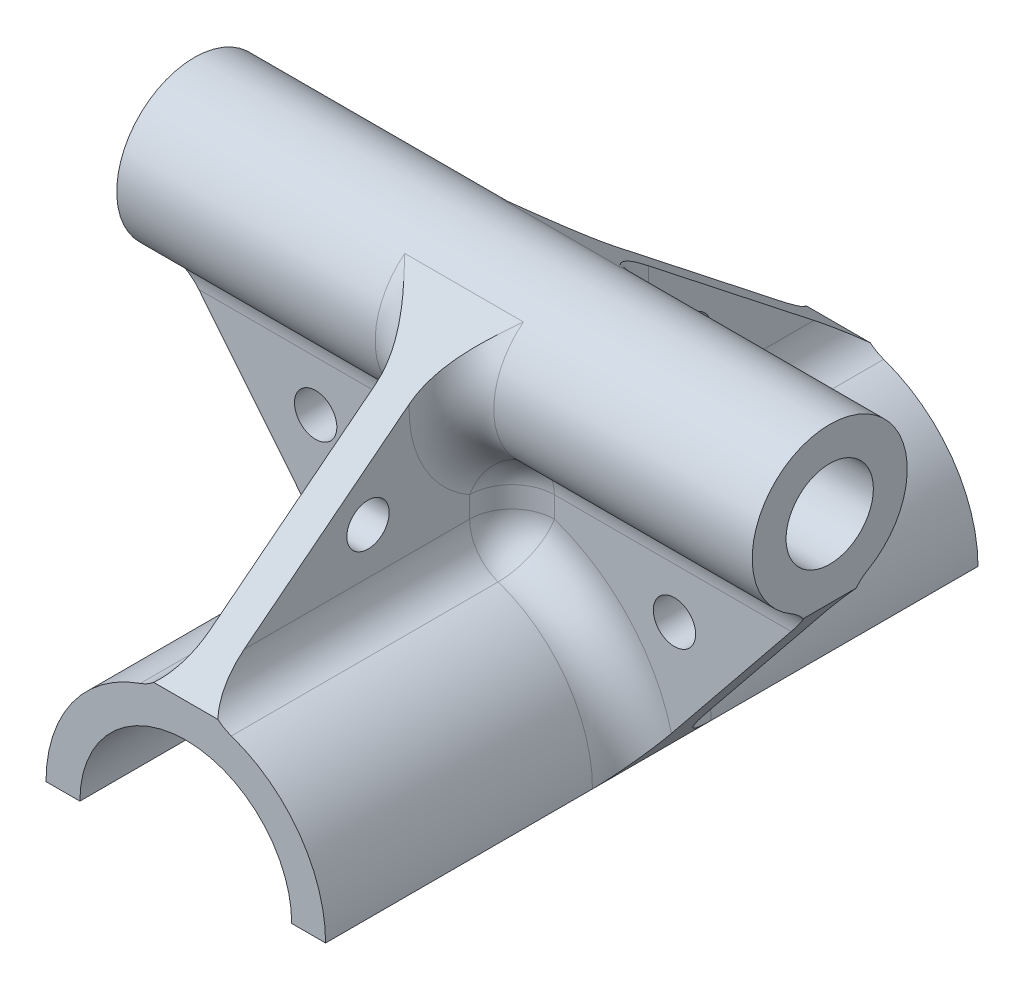
SolidWorks part; units mm, degrees
material "ABS"
ref_plane "Front Plane" through (0, 0, 0) normal (0, 0, 1) x (1, 0, 0)
ref_plane "Top Plane" through (0, 0, 0) normal (0, 1, 0) x (1, 0, 0)
ref_plane "Right Plane" through (0, 0, 0) normal (1, 0, 0) x (0, 0, -1)
sketch "Sketch2" plane through (0, 0, 0) normal (0, 0, 1) x (1, 0, 0)
  line L0 (-16.5, 0) -> (-12.5, 0)
  line L1 (12.5, 0) -> (16.5, 0)
  arc A0 (16.5, 0) -> (-16.5, 0) centre (0, 0) ccw
  arc A1 (12.5, 0) -> (-12.5, 0) centre (0, 0) ccw
  dimension "D1" = 4
  dimension "D2" = 25
extrude "Fuselage mount" add sketch "Sketch2" along normal blind 77
sketch "Sketch3" plane through (0, 0, 0) normal (1, 0, 0) x (0, 0, -1)
  line L0 (-38.5, 16.5) -> (-38.5, 35.1181) construction
  line L1 (0, 16.5) -> (-77, 16.5) construction
  circle A0 centre (-38.5, 35.1181) radius 9.15
  circle A1 centre (-38.5, 35.1181) radius 5.15
  dimension "D2" = 10.3
  dimension "D3" = 18.6181
  dimension "D1" = 4
extrude "Spar mount" add sketch "Sketch3" along normal blind 37.5 and the other way blind 37.5 separate body
ref_plane "Plane1" through (0, 0, 38.5) normal (0, 0, 1) x (1, 0, 0)
sketch "Sketch8" plane through (0, 0, 0) normal (1, 0, 0) x (0, 0, -1)
  line L0 (-77, 16.5) -> (-44.1537, 42.3124)
  line L1 (0, 16.5) -> (-32.8463, 42.3124)
  line L2 (-77, 16.5) -> (-77, 12.5)
  line L3 (-77, 16.5) -> (-77, 0) construction
  line L4 (-77, 12.5) -> (0, 12.5)
  line L5 (0, 0) -> (0, 16.5) construction
  line L6 (0, 12.5) -> (0, 16.5)
  circle A0 centre (-38.5, 35.1181) radius 9.15 construction
  arc A1 (-44.1537, 42.3124) -> (-32.8463, 42.3124) centre (-38.5, 35.1181) ccw
extrude "Boss-Extrude1" add sketch "Sketch8" along normal blind 2 and the other way blind 2
sketch "Sketch9" plane through (0, 0, 38.5) normal (0, 0, 1) x (1, 0, 0)
  line L0 (-16.5, 0) -> (-37.5, 25.9681)
  line L1 (-37.5, 25.9681) -> (-37.5, 29.9681)
  line L2 (-37.5, 44.2681) -> (-37.5, 25.9681) construction
  line L3 (-37.5, 29.9681) -> (-2, 29.9681)
  line L4 (-2, 42.3124) -> (-2, 25.9681) construction
  line L5 (-2, 29.9681) -> (-2, 16.3783)
  line L8 (0, 0) -> (0, 50000) construction
  line L9 (2, 29.9681) -> (2, 16.3783)
  line L10 (37.5, 29.9681) -> (2, 29.9681)
  line L11 (37.5, 25.9681) -> (37.5, 29.9681)
  line L12 (16.5, 0) -> (37.5, 25.9681)
  arc A0 (-16.5, 0) -> (-2, 16.3783) centre (0, 0) cw
  arc A1 (-2, 16.3783) -> (-16.5, 0) centre (0, 0) ccw construction
  arc A2 (16.5, 0) -> (2, 16.3783) centre (0, 0) ccw
extrude "Boss-Extrude2" add sketch "Sketch9" along normal blind 2 and the other way blind 2
fillet "Fillet1" radius 5 20 edges at (-2, 33.0959, 47.4237) (-2, 16.3783, 58.75) (-2, 21.2838, 40.5) (-12.3541, 10.9373, 40.5) (-19.75, 26.1894, 40.5) (-2, 33.0959, 29.5763) (-2, 21.2838, 36.5) (-19.75, 26.1894, 36.5) (-12.3541, 10.9373, 36.5) (-2, 16.3783, 18.25) (19.75, 26.1894, 40.5) (19.75, 26.1894, 36.5) (2, 33.0959, 29.5763) (12.3541, 10.9373, 36.5) (2, 21.2838, 36.5) (2, 16.3783, 18.25) (2, 33.0959, 47.4237) (2, 21.2838, 40.5) (2, 16.3783, 58.75) (12.3541, 10.9373, 40.5)
sketch "Sketch10" plane through (2, 0, 0) normal (1, 0, 0) x (0, 0, -1)
  line L0 (-4.8718, 20.3286) -> (-26.1375, 28.2339) construction
  line L1 (-38.5, 35.69) -> (-38.5, -49964.31) construction
  line L2 (-14.6158, 27.9859) -> (-31.5, 20.3286) construction
  line L4 (-31.5, 20.3286) -> (-4.8718, 20.3286) construction
  line L5 (-4.8718, 20.3286) -> (-24.3597, 35.6432) construction
  arc A3 (-31.5, 22.8208) -> (-24.3597, 35.6432) centre (-38.5, 35.1181) ccw construction
  point P0 (-19.5052, 25.7684)
  point P1 (-57.4948, 25.7684)
hole_wizard "Ø5.0 (5) Diameter Hole1" positions "Sketch10" profile "Sketch12" hole size "Ø5.0" standard "ANSI Metric" end condition through all
sketch "Sketch12" plane through (2, 25.7684, 19.5052) normal (0, 1, 0) x (0, 0, -1)
  line L0 (0, 0) -> (0, 39.5)
  line L1 (0, 39.5) -> (2.5, 39.5)
  line L2 (2.5, 39.5) -> (2.5, 0)
  line L5 (2.5, 0) -> (0, 0)
  line L11 (0, -6.35) -> (0, 107.95) construction
  dimension "Thru Hole Dia." = 5
  dimension "Thru Hole Depth" = 39.5
sketch "Sketch13" plane through (0, 0, 36.5) normal (0, 0, -1) x (-1, 0, 0)
  line L0 (-34.9549, 22.8208) -> (-15.8006, 14.5805) construction
  line L1 (-7, 22.8208) -> (-27.8896, 14.0841) construction
  line L2 (-20.8244, 5.3474) -> (-34.9549, 22.8208) construction
  line L3 (0, 0) -> (0, 50000) construction
  arc A0 (-7, 20.3286) -> (-20.8244, 5.3474) centre (0, 0) ccw construction
  point P11 (-21.1747, 16.8925)
  point P15 (21.1747, 16.8925)
hole_wizard "Ø5.0 (5) Diameter Hole2" positions "Sketch13" profile "Sketch14" hole size "Ø5.0" standard "ANSI Metric" end condition through all
sketch "Sketch14" plane through (-21.1747, 16.8925, 36.5) normal (1, 0, 0) x (0, 1, 0)
  line L0 (0, 0) -> (0, 40.5)
  line L1 (0, 40.5) -> (2.5, 40.5)
  line L2 (2.5, 40.5) -> (2.5, 0)
  line L5 (2.5, 0) -> (0, 0)
  line L11 (0, -6.35) -> (0, 107.95) construction
  dimension "Thru Hole Dia." = 5
  dimension "Thru Hole Depth" = 40.5
equation "\"Diameter\"= 10mm"
equation "\"Height\"= 19.19mm - 0.5719"
equation "\"D2@Sketch3\"=\"Diameter\"+.3mm"
equation "\"D3@Sketch3\"=\"Height\""
